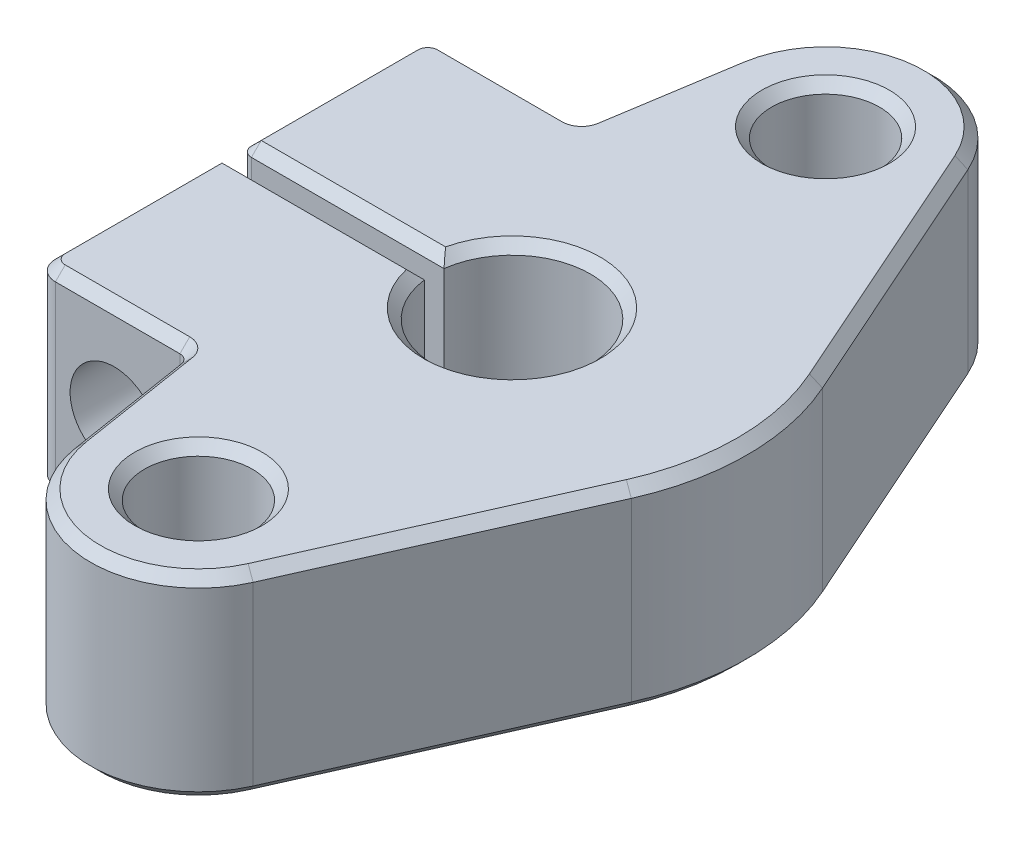
SolidWorks part; units mm, degrees
ref_plane "前视基准面" through (0, 0, 0) normal (0, 0, 1) x (1, 0, 0)
ref_plane "上视基准面" through (0, 0, 0) normal (0, 1, 0) x (1, 0, 0)
ref_plane "右视基准面" through (0, 0, 0) normal (1, 0, 0) x (0, 0, -1)
sketch "草图1" plane through (0, 0, 0) normal (0, 1, 0) x (1, 0, 0)
  line L0 (-12.1257, 0) -> (12, 0) construction
  line L1 (0, 18.2531) -> (0, -17.0921) construction
  line L2 (-12.1257, -16) -> (12, -16) construction
  line L3 (-12.1257, 16) -> (12, 16) construction
  line L4 (5.0257, -18.2344) -> (10.9651, -4.875)
  line L5 (-14.2966, -10) -> (-2.9072, -10)
  line L6 (5.0257, 18.2344) -> (10.9651, 4.875)
  line L7 (-14.2966, 10) -> (-2.9072, 10)
  line L8 (-14.2966, 0) -> (-2.9072, 0)
  line L9 (-14.2966, -0.5) -> (-2.9072, -0.5)
  line L10 (-14.2966, 0.5) -> (-2.9072, 0.5)
  line L11 (-14.2966, 0.5) -> (-14.2966, -0.5)
  line L12 (-2.9072, 0.5) -> (-2.9072, -0.5)
  line L13 (-14.2966, 10) -> (-14.2966, 0.5)
  line L14 (-14.2966, -0.5) -> (-14.2966, -10)
  line L15 (-5.4324, 16.8594) -> (-7.9017, 1.25)
  line L16 (-5.4324, -16.8594) -> (-7.9017, -1.25)
  circle A0 centre (0, 0) radius 4
  circle A1 centre (0, 16) radius 2.75
  circle A2 centre (0, -16) radius 2.75
  circle A3 centre (0, 16) radius 5.5
  circle A4 centre (0, -16) radius 5.5
  circle A5 centre (0, 0) radius 12
  circle A6 centre (0, 0) radius 8
  dimension "D1" = 8
  dimension "D4" = 5.5
  dimension "D5" = 5.5
  dimension "D6" = 11
  dimension "D7" = 11
  dimension "D10" = 24
  dimension "D13" = 16
  dimension "D11" = 10
  dimension "D8" = 0.5
  dimension "D2" = 16
  dimension "D3" = 16
  dimension "D9" = 0.5
  dimension "D12" = 10
extrude "凸台-拉伸1" add sketch "草图1" along normal blind 10 contours A6 L10 A0 L9 | A6 L16 A5 A4 A3 L15 | A5 L6 A3 | A5 A3 A1 | A5 A3 L15 | A5 L7 L13 L10 | A6 L15 L7 A5 L10 | A5 L9 L14 L5 | A6 L9 A5 L5 L16 | A5 L16 A4 | A5 A4 A2 | A5 A4 L4 | A3 A5 | A4 A5 region at (6.5539, 0, 11.8265) region at (-0.6976, 0, 21.306) region at (7.6486, 0, 8.8472) region at (-5.261, 0, 12.3489) region at (0, 0, 11.3063) region at (6.5539, 0, -11.8265) region at (-9.1413, 0, 4.3368) region at (-12.0226, 0, 6.2518) region at (5.2351, 0, -17.1113) region at (0, 0, -11.3063) region at (-7.7271, 0, 0.8512) region at (-5.261, 0, -12.3489) region at (-9.1413, 0, -4.3368) region at (-12.0226, 0, -6.2518)
sketch "草图3" plane through (0, 0, 10) normal (0, 0, 1) x (1, 0, 0)
  line L0 (-14.2966, 5) -> (-1.8681, 5) construction
  line L1 (-14.2966, 10) -> (-14.2966, 0) construction
  line L2 (-14.2966, 10) -> (-14.2966, 0) construction
  line L3 (-10.2966, 10) -> (-10.2966, 0) construction
  circle A0 centre (-10.2966, 5) radius 1.65
  circle A1 centre (-10.2966, 5) radius 2.25
  dimension "D2" = 3.3
  dimension "D3" = 4.5
  dimension "D1" = 4
extrude "切除-拉伸1" cut sketch "草图3" against normal up to next contours A1
extrude "切除-拉伸2" cut sketch "草图3<3>" against normal through all contours A0
sketch "草图3<3>" plane through (0, 0, 10) normal (0, 0, 1) x (1, 0, 0) same geometry as "草图3"
fillet "圆角1" radius 1 2 edges at (-14.2966, 5, -10) (-14.2966, 5, 10)
fillet "圆角2" radius 0.5 4 edges at (-6.5176, 5, 10) (-14.2966, 5, -0.5) (-14.2966, 5, 0.5) (-6.5176, 5, -10)
chamfer "倒角1" distance 0.5 angle 45 44 edges at (0, 10, 18.75) (0, 10, -13.25) (-14.0037, 10, -9.7071) (-10.1206, 10, -10) (-6.6199, 10, -10.1198) (-5.9416, 10, -13.6406) (-0.717, 10, -21.4531) (7.9954, 10, -11.5547) (12, 10, 0) (7.9954, 10, 11.5547) (-0.717, 10, 21.4531) (-5.9416, 10, 13.6406) (-6.6199, 10, 10.1198) (-10.1206, 10, 10) (-14.0037, 10, 9.7071) (-14.2966, 10, 5) (-14.1502, 10, 0.6464) (-8.8826, 10, 0.5) (4, 10, 0) (-8.8826, 10, -0.5) (-14.1502, 10, -0.6464) (-14.2966, 10, -5) (0, 0, 18.75) (0, 0, -13.25) (4, 0, 0) (-8.8826, 0, 0.5) (-14.1502, 0, 0.6464) (-14.2966, 0, 5) (-14.0037, 0, 9.7071) (-10.1206, 0, 10) (-6.6199, 0, 10.1198) (-5.9416, 0, 13.6406) (-0.717, 0, 21.4531) (7.9954, 0, 11.5547) (12, 0, 0) (7.9954, 0, -11.5547) (-0.717, 0, -21.4531) (-5.9416, 0, -13.6406) (-6.6199, 0, -10.1198) (-10.1206, 0, -10) (-14.0037, 0, -9.7071) (-14.2966, 0, -5) (-14.1502, 0, -0.6464) (-8.8826, 0, -0.5)
